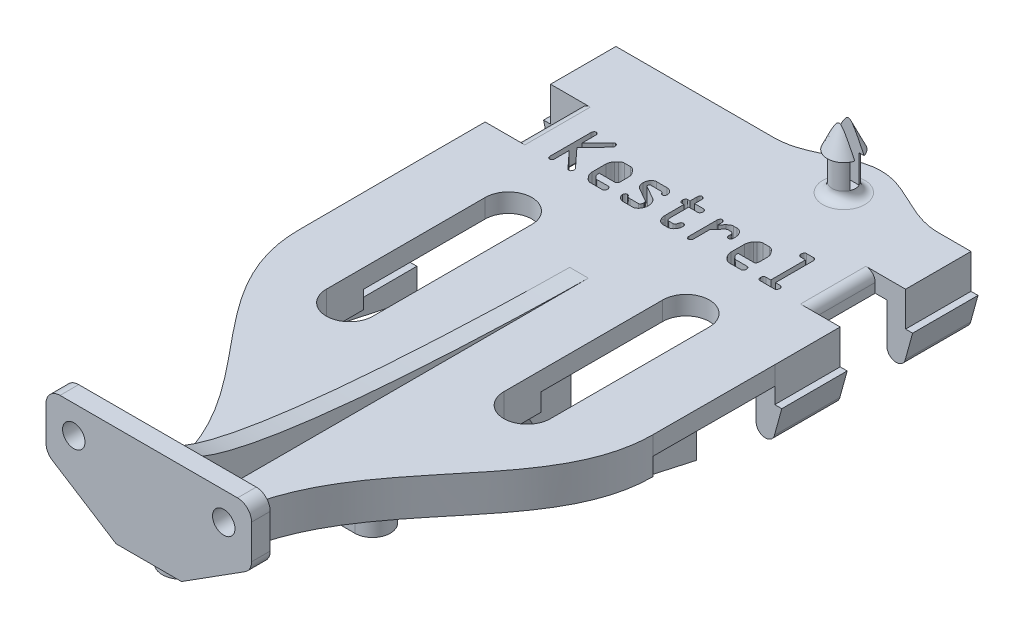
SolidWorks part; units mm, degrees
ref_plane "Front Plane" through (0, 0, 0) normal (0, 0, 1) x (1, 0, 0)
ref_plane "Top Plane" through (0, 0, 0) normal (0, 1, 0) x (1, 0, 0)
ref_plane "Right Plane" through (0, 0, 0) normal (1, 0, 0) x (0, 0, -1)
sketch "Sketch1" plane through (0, 0, 0) normal (0, 1, 0) x (1, 0, 0)
  line L0 (-19, 0) -> (-8.5, 0)
  line L1 (-19, 0) -> (-19, 5)
  line L2 (-19, 5) -> (19, 5)
  line L3 (19, 5) -> (19, 0)
  line L4 (0, 0) -> (0, -8) construction
  line L5 (0, -8) -> (0, -15) construction
  line L6 (-3.5, -15) -> (3.5, -15)
  line L7 (-3.5, -15) -> (-3.5, -5)
  line L8 (3.5, -15) -> (3.5, -5)
  line L9 (8.5, 0) -> (19, 0)
  arc A0 (3.5, -5) -> (8.5, 0) centre (8.5, -5) cw
  arc A1 (-3.5, -5) -> (-8.5, 0) centre (-8.5, -5) ccw
  point P4 (0, 0)
  point P14 (0, -15)
  point P17 (3.5, 0)
  dimension "D1" = 5
extrude "Boss-Extrude1" add sketch "Sketch1" along normal blind 2
sketch "Sketch2" plane through (0, 0, 0) normal (0, -1, 0) x (1, 0, 0)
  line L0 (-3.5, 15) -> (3.5, 15)
  line L1 (3.5, 15) -> (3.5, 13)
  line L2 (3.5, 15) -> (3.5, 5) construction
  line L3 (3.5, 13) -> (-3.5, 13)
  line L4 (-3.5, 5) -> (-3.5, 15) construction
  line L5 (-3.5, 13) -> (-3.5, 15)
extrude "Boss-Extrude2" add sketch "Sketch2" along normal blind 1.7
sketch "Sketch3" plane through (0, -1.7, 0) normal (0, -1, 0) x (1, 0, 0)
  line L0 (-3.5, 15) -> (-3.5, 6.3)
  line L1 (-3.5, 6.3) -> (3.5, 6.3)
  line L2 (3.5, 6.3) -> (3.5, 15)
  line L3 (3.5, 15) -> (-3.5, 15)
extrude "Boss-Extrude3" add sketch "Sketch3" along normal blind 2
sketch "Sketch5" plane through (0, 0, 0) normal (0, 0, 1) x (1, 0, 0)
  line L0 (0, -3.7) -> (0, 2) construction
  line L1 (3.5, -3.7) -> (-3.5, -3.7) construction
  line L2 (-3.5, 2) -> (3.5, 2) construction
  line L3 (-19, 0) -> (-19, -1.7)
  line L4 (-19, -1.7) -> (-19.75, -1.7)
  line L5 (-19, 0) -> (-17, 0)
  line L6 (-19, 0) -> (-8.5, 0) construction
  line L7 (-17, 0) -> (-17, -4.2915)
  line L9 (-19.75, -1.7) -> (-18.9642, -4.5567)
  line L10 (19.75, -1.7) -> (18.9642, -4.5567)
  line L11 (17, 0) -> (17, -4.2915)
  line L12 (19, 0) -> (17, 0)
  line L13 (19, -1.7) -> (19.75, -1.7)
  line L14 (19, 0) -> (19, -1.7)
  arc A0 (-17, -4.2915) -> (-18.9642, -4.5567) centre (-18, -4.2915) cw
  arc A1 (17, -4.2915) -> (18.9642, -4.5567) centre (18, -4.2915) ccw
  dimension "D1" = 1
extrude "Boss-Extrude5" add sketch "Sketch5" against normal up to surface (5 mm away) up to face at (0, 1, -5)
sketch "Sketch12" plane through (-3.5, 0, 0) normal (-1, 0, 0) x (0, 0, 1)
  line L0 (15, 2) -> (15, -3.7)
  line L1 (15, -0.85) -> (48, -0.85) construction
  line L2 (48, -1.85) -> (48, 0.15)
  line L5 (5, 2) -> (15, 2) construction
  line L6 (5, 2) -> (15, 2) construction
  line L7 (48, 0.15) -> (51.4434, 0.15) construction
  spline S0 degree 3 poles (48, 0.15) (45.4313, 0.15) (17.4134, 2) (15, 2) knots 0 0 0 0 1 1 1 1
  spline S1 degree 3 poles (48, -1.85) (45.4313, -1.85) (17.4134, -3.7) (15, -3.7) knots 0 0 0 0 1 1 1 1
  point P9 (48, -0.85)
extrude "Boss-Extrude10" add sketch "Sketch12" against normal up to surface (7 mm away) contours S0 L0 S1 L2 up to face at (3.5, -0.85, 9.825)
sketch "Sketch6" plane through (0, 0, 48) normal (0, 0, 1) x (1, 0, 0)
  line L0 (0, 8.9074) -> (0, 5.9074) construction
  line L1 (-8.025, 5.9074) -> (8.025, 5.9074) construction
  line L2 (-9.5, 8.9074) -> (9.5, 8.9074)
  line L3 (-11, 7.4074) -> (-11, 3.7322)
  line L4 (-10.3035, 2.4655) -> (-3.5, -1.85)
  line L5 (-3.5, -1.85) -> (3.5, -1.85)
  line L6 (11, 7.4074) -> (11, 3.7322)
  line L7 (10.3035, 2.4655) -> (3.5, -1.85)
  line L8 (3.5, -1.85) -> (-3.5, -1.85) construction
  line L9 (-3.5, -1.85) -> (3.5, -1.85)
  line L11 (3.5, -1.85) -> (-3.5, -1.85)
  line L12 (3.5, -1.85) -> (-3.5, -1.85)
  circle A0 centre (-8.025, 5.9074) radius 1.2
  circle A1 centre (8.025, 5.9074) radius 1.2
  arc A2 (11, 3.7322) -> (10.3035, 2.4655) centre (9.5, 3.7322) cw
  arc A3 (9.5, 8.9074) -> (11, 7.4074) centre (9.5, 7.4074) cw
  arc A4 (-9.5, 8.9074) -> (-11, 7.4074) centre (-9.5, 7.4074) ccw
  arc A5 (-11, 3.7322) -> (-10.3035, 2.4655) centre (-9.5, 3.7322) ccw
  point P5 (0, 5.9074)
  point P12 (0, 8.9074)
  dimension "D1" = 1.5
extrude "Boss-Extrude6" add sketch "Sketch6" against normal blind 2 contours L3 A5 L4 L7 A2 L6 A3 L2 A4 A0 A1 region at (0, 4.1004, 48)
sketch "Sketch8" plane through (0, 0, 0) normal (1, 0, 0) x (0, 0, -1)
  line L0 (-48, -1.85) -> (-17.2473, -11.6027)
sketch3d "3DSketch2"
  line L0 (3.5, -1.85, 48) -> (-3.5, -1.85, 48) construction
  line L1 (0, -1.85, 48) -> (0, -11.6027, 17.2473) construction
sketch "Sketch9" plane through (0, -29.0291, -37.7024) normal (0, 0.9532, -0.3023) x (1, 0, 0)
  line L0 (0, -51.7402) -> (0, -54.7402) construction
  line L1 (-8.025, -54.7402) -> (8.025, -54.7402) construction
  line L2 (-9.5, -51.7402) -> (9.5, -51.7402)
  line L3 (-11, -53.2402) -> (-11, -56.9154)
  line L4 (-10.3035, -58.182) -> (-3.5, -62.4976)
  line L5 (-3.5, -62.4976) -> (3.5, -62.4976)
  line L6 (11, -53.2402) -> (11, -56.9154)
  line L7 (10.3035, -58.182) -> (3.5, -62.4976)
  line L8 (3.5, -89.9089) -> (-3.5, -89.9089) construction
  line L9 (-3.5, -57.2253) -> (3.5, -57.2253) construction
  line L10 (0, -57.2253) -> (0, -62.4976) construction
  line L11 (3.5, -62.4976) -> (-3.5, -62.4976) construction
  line L12 (3.5, -89.9089) -> (-3.5, -89.9089)
  line L13 (-3.5, -62.4976) -> (3.5, -62.4976)
  circle A0 centre (-8.025, -54.7402) radius 1.2
  circle A1 centre (8.025, -54.7402) radius 1.2
  arc A2 (11, -56.9154) -> (10.3035, -58.182) centre (9.5, -56.9154) cw
  arc A3 (9.5, -51.7402) -> (11, -53.2402) centre (9.5, -53.2402) cw
  arc A4 (-9.5, -51.7402) -> (-11, -53.2402) centre (-9.5, -53.2402) ccw
  arc A5 (-11, -56.9154) -> (-10.3035, -58.182) centre (-9.5, -56.9154) ccw
  point P5 (0, -54.7402)
  point P12 (0, -51.7402)
  point P30 (0, -62.4976)
  dimension "D1" = 1.5
extrude "Boss-Extrude8" [suppressed] add sketch "Sketch9" along normal blind 2 contours A5 L3 A4 L2 A3 L6 A2 L7 L5 L4 A0 A1
sketch "Sketch11" plane through (0, 0, -5) normal (0, 0, -1) x (-1, 0, 0)
  line L10 (-19, 2) -> (-19, -1.7)
  line L11 (-19, -1.7) -> (-19.75, -1.7)
  line L12 (-19.75, -1.7) -> (-18.9642, -4.5567)
  line L13 (-17, -4.2915) -> (-17, 0)
  line L14 (-17, 0) -> (17, 0)
  line L15 (17, 0) -> (17, -4.2915)
  line L16 (18.9642, -4.5567) -> (19.75, -1.7)
  line L17 (19.75, -1.7) -> (19, -1.7)
  line L18 (19, -1.7) -> (19, 2)
  line L19 (19, 2) -> (-19, 2)
  line L20 (-19, 2) -> (-19, -1.7)
  line L21 (-19, -1.7) -> (-19.75, -1.7)
  line L22 (-19.75, -1.7) -> (-18.9642, -4.5567)
  line L23 (-17, -4.2915) -> (-17, 0)
  line L24 (-17, 0) -> (17, 0)
  line L25 (17, 0) -> (17, -4.2915)
  line L26 (18.9642, -4.5567) -> (19.75, -1.7)
  line L27 (19.75, -1.7) -> (19, -1.7)
  line L28 (19, -1.7) -> (19, 2)
  line L29 (19, 2) -> (-19, 2)
  arc A2 (-18.9642, -4.5567) -> (-17, -4.2915) centre (-18, -4.2915) ccw
  arc A3 (17, -4.2915) -> (18.9642, -4.5567) centre (18, -4.2915) ccw
  arc A4 (-18.9642, -4.5567) -> (-17, -4.2915) centre (-18, -4.2915) ccw
  arc A5 (17, -4.2915) -> (18.9642, -4.5567) centre (18, -4.2915) ccw
  dimension "D1" = 0
extrude "Boss-Extrude9" add sketch "Sketch11" along normal blind 5
sketch "Sketch13" plane through (0, 0, -10) normal (0, 0, -1) x (-1, 0, 0)
  line L0 (-17, 0) -> (-17, 2)
  line L1 (17, 0) -> (17, 2)
  line L2 (-17, 2) -> (-19, 2)
  line L10 (19, 2) -> (-19, 2)
  line L11 (-19, 2) -> (-19, -1.7)
  line L12 (-19, -1.7) -> (-19.75, -1.7)
  line L13 (-19.75, -1.7) -> (-18.9642, -4.5567)
  line L14 (-17, -4.2915) -> (-17, 0)
  line L15 (-17, 0) -> (17, 0)
  line L16 (17, 0) -> (17, -4.2915)
  line L17 (18.9642, -4.5567) -> (19.75, -1.7)
  line L18 (19.75, -1.7) -> (19, -1.7)
  line L19 (19, -1.7) -> (19, 2)
  line L20 (19, 2) -> (17, 2)
  line L21 (-19, 2) -> (-19, -1.7)
  line L22 (-19, -1.7) -> (-19.75, -1.7)
  line L23 (-19.75, -1.7) -> (-18.9642, -4.5567)
  line L24 (-17, -4.2915) -> (-17, 0)
  line L26 (17, 0) -> (17, -4.2915)
  line L27 (18.9642, -4.5567) -> (19.75, -1.7)
  line L28 (19.75, -1.7) -> (19, -1.7)
  line L29 (19, -1.7) -> (19, 2)
  arc A2 (-18.9642, -4.5567) -> (-17, -4.2915) centre (-18, -4.2915) ccw
  arc A3 (17, -4.2915) -> (18.9642, -4.5567) centre (18, -4.2915) ccw
  arc A4 (-18.9642, -4.5567) -> (-17, -4.2915) centre (-18, -4.2915) ccw
  arc A5 (17, -4.2915) -> (18.9642, -4.5567) centre (18, -4.2915) ccw
  dimension "D1" = 0
extrude "Boss-Extrude11" add sketch "Sketch13" along normal blind 11
sketch "Sketch14" [suppressed] plane through (0, 0, 0) normal (1, 0, 0) x (0, 0, -1)
  line L0 (-21.4898, -4.5318) -> (-16.4946, -9.5269) construction
  line L2 (-19.0398, -6.9817) -> (-21.6386, -4.383) construction
  line L4 (-25, 3.9255) -> (-25, 7.5698) construction
  line L6 (-25, 9.4074) -> (-25, 5.7322) construction
  line L8 (-21.4898, -4.5318) -> (-23.7806, -2.241)
  line L9 (-23.7806, -2.241) -> (-20.5918, -2.8431)
  line L10 (-25, 3.9255) -> (-25, 0.342)
  line L51 (-25, 0.342) -> (-21.429, 0.9803)
  arc A0 (-21.429, 0.9803) -> (-25, 3.9255) centre (-22, 3.9255) cw
  arc A1 (-21.4898, -4.5318) -> (-20.5918, -2.8431) centre (-20.7827, -3.8247) cw
  spline S0 degree 3 poles (2744.4383, -1158.1805) (-2916.1759, 1174.945) (2874.0779, -1177.5151) (-2786.653, 1143.8803) knots -6.32124 -6.32124 -6.32124 -6.32124 7.304164 7.304164 7.304164 7.304164 only from (-23.7806, -2.241) to (-15, -3.7) construction
  spline S1 degree 3 poles (-2786.706, -1145.6021) (2873.7453, 1175.6786) (-2915.4391, -1176.3458) (2743.3321, 1156.0245) knots -6.104431 -6.104431 -6.104431 -6.104431 7.520128 7.520128 7.520128 7.520128 only from (-15, 2) to (-25, 0.342) construction
  spline S2 degree 3 poles (-20.5918, -2.8431) (-18.3357, -3.2818) (-16.1475, -3.7) (-15, -3.7) knots 0.524559 0.524559 0.524559 0.524559 1 1 1 1 construction
  spline S3 degree 3 poles (-15, 2) (-16.2892, 2) (-18.8922, 1.4721) (-21.429, 0.9803) knots 0.199776 0.199776 0.199776 0.199776 0.733944 0.733944 0.733944 0.733944 construction
  dimension "D1" = 3
  dimension "D2" = 1
extrude "Boss-Extrude12" [suppressed] add sketch "Sketch14" along normal blind 1 and the other way blind 1 contours L51 A0 L10 | L8 A1 L9
fillet "Fillet1" [suppressed] radius 3
sketch "Sketch18" plane through (0, 0, 0) normal (1, 0, 0) x (0, 0, -1)
  line L0 (-46, 8.5867) -> (-46, 16.5411)
  line L1 (0, 2) -> (9.2636, 2.3571)
  line L2 (-46, 8.5867) -> (-46, 0.2267)
  line L3 (-46, 0.2267) -> (0, 2)
  spline S0 degree 3 poles (-46, 8.5867) (-46, 2.3837) (-1.9861, 1.9234) (0, 2) knots 0 0 0 0 1 1 1 1
  point P5 (-46, 0.2267)
extrude "Boss-Extrude16" add sketch "Sketch18" along normal blind 1 and the other way blind 1 contours L2 L3 region at (0, 2.6128, 33.5816)
sketch "Sketch19" plane through (0, 0, -10) normal (0, 0, -1) x (-1, 0, 0)
  line L4 (-17, 0) -> (17, 0)
  line L5 (17, 0) -> (17, 2)
  line L6 (17, 2) -> (-17, 2)
  line L7 (-17, 2) -> (-17, 0)
  line L8 (-17, 0) -> (17, 0)
  line L9 (17, 0) -> (17, 2)
  line L10 (17, 2) -> (-17, 2)
  line L11 (-17, 2) -> (-17, 0)
  dimension "D1" = 0
extrude "Boss-Extrude17" add sketch "Sketch19" along normal up to surface (11 mm away) up to face at (18.433, -1.5178, -21)
sketch "Sketch20" plane through (0, 2, 0) normal (0, 1, 0) x (1, 0, 0)
  line L0 (-19.75, 0) -> (-19.75, 21) construction
  line L1 (19.75, 0) -> (19.75, 21) construction
  line L4 (-23.75, 14) -> (-15.75, 14)
  line L5 (-23.75, 14) -> (-23.75, 7)
  line L6 (-23.75, 7) -> (-15.75, 7)
  line L7 (-15.75, 14) -> (-15.75, 7)
  line L8 (-23.75, 14) -> (-15.75, 7) construction
  line L9 (-23.75, 7) -> (-15.75, 14) construction
  line L10 (15.75, 14) -> (23.75, 14)
  line L11 (15.75, 14) -> (15.75, 7)
  line L12 (15.75, 7) -> (23.75, 7)
  line L13 (23.75, 14) -> (23.75, 7)
  line L14 (15.75, 14) -> (23.75, 7) construction
  line L15 (15.75, 7) -> (23.75, 14) construction
  point P6 (-19.75, 10.5)
  point P15 (19.75, 10.5)
extrude "Cut-Extrude2" cut sketch "Sketch20" against normal blind 10.2
fillet "Fillet3" radius 1 2 edges at (15.75, 2, -10.5) (-15.75, 2, -10.5)
sketch "Sketch22" plane through (0, 2, 0) normal (0, 1, 0) x (1, 0, 0)
  line L0 (-15.75, 7) -> (15.75, 7) construction
  text T0 "Kestrel" font "OCR A Extended" height 5
extrude "Cut-Extrude4" cut sketch "Sketch22" against normal up to surface (2 mm away) up to face at (0, 0, -5.1151)
delete or keep bodies "Body-Delete/Keep 1" type delete bodies bodies 125 126
sketch "Sketch23" plane through (0, 2, 0) normal (0, 1, 0) x (1, 0, 0)
  circle A0 centre (6.7297, 19.6566) radius 1.375 construction
  circle A1 centre (6.7297, 19.6566) radius 1.375 construction
  circle A2 centre (6.7297, 19.6566) radius 1.25
sketch "Sketch25" plane through (0, 2, 0) normal (0, 1, 0) x (1, 0, 0)
  line L0 (-19, 21) -> (19, 21) construction
  line L1 (15.4974, 21) -> (27.7055, 21) construction
  line L2 (10.4974, 21) -> (15.4974, 21)
  line L3 (2.9621, 21) -> (-2.0379, 21)
  line L4 (-2.0379, 21) -> (-6.3002, 21) construction
  line L5 (2.9621, 21) -> (10.4974, 21)
  circle A0 centre (6.7297, 19.6566) radius 4 construction
  spline S0 degree 3 poles (6.7297, 23.6566) (9.7835, 23.6566) (12.1916, 21) (15.4974, 21) knots 0 0 0 0 1 1 1 1
  spline S1 degree 3 poles (-2.0379, 21) (1.2679, 21) (3.676, 23.6566) (6.7297, 23.6566) knots 0 0 0 0 1 1 1 1
extrude "Boss-Extrude18" add sketch "Sketch25" against normal up to surface (2 mm away) contours L3 S1 S0 L2 L5 up to face at (-7.4332, 0, -8.6263)
extrude "Boss-Extrude19" add sketch "Sketch23" along normal blind 4
fillet "Fillet5" radius 1 1 edges at (6.7297, 2, -18.4066)
sketch "Sketch27" plane through (0, 2, 0) normal (0, 1, 0) x (1, 0, 0)
  line L0 (-19, 0) -> (19, 0)
  line L1 (-3.5, -15) -> (3.5, -15)
  line L3 (0, 0) -> (0, 4.6764) construction
  line L4 (-3.5, -15) -> (-3.5, -46) construction
  spline S0 degree 2 poles (-19, 0) (-3.5, -6.737) (-3.5, -15) knots 0 0 0 1 1 1
  spline S1 degree 2 poles (19, 0) (3.5, -6.737) (3.5, -15) knots 0 0 0 1 1 1
extrude "Boss-Extrude20" add sketch "Sketch27" against normal up to surface (2 mm away) up to face at (-7.4332, 0, -8.6263)
sketch "Sketch28" plane through (0, 0, 0) normal (0, -1, 0) x (1, 0, 0)
  line L0 (-3.5, 13) -> (-18.9642, 13)
  line L1 (3.5, 13) -> (18.9642, 13)
  line L2 (-18.9642, 0) -> (-18.9642, 13) construction
  line L3 (18.9642, 13) -> (18.9642, 0) construction
  line L4 (-3.5, 47.0417) -> (-3.5, 45.0417) construction
  line L5 (-3.5, 48) -> (-3.5, 15) construction
  line L6 (3.5, 47.0417) -> (3.5, 45.0417)
  line L7 (3.5, 15) -> (3.5, 48) construction
  line L8 (0, 15) -> (0, 21.0954) construction
  line L9 (3.5, 15) -> (-3.5, 15) construction
  line L10 (-3.5, 13) -> (3.5, 13)
  line L12 (-3.5, 45.0417) -> (3.5, 45.0417)
  spline S0 degree 3 poles (-18.9642, 13) (-18.9642, 24.9756) (-3.5, 30.7082) (-3.5, 45.0417) knots 0 0 0 0 1 1 1 1
  spline S1 degree 3 poles (18.9642, 13) (18.9642, 24.9756) (3.5, 30.7082) (3.5, 45.0417) knots 0 0 0 0 1 1 1 1
  point P9 (0, 0)
extrude "Boss-Extrude21" add sketch "Sketch28" along normal blind 1.9 contours L12 S0 L0 L10 L1 S1
sketch "Sketch29" plane through (-3.5, 0, 0) normal (-1, 0, 0) x (0, 0, 1)
  line L0 (6.3, -3.7) -> (6.3, -10.4)
  line L1 (13, -3.7) -> (6.3, -3.7)
  line L2 (6.3, -10.4) -> (3.1823, -10.4) construction
  spline S0 degree 3 poles (6.3, -10.4) (9.9895, -10.4) (9.9638, -3.7) (13, -3.7) knots 0 0 0 0 1 1 1 1
  line M3 (6.3, -3.7) -> (15, -3.7)
extrude "Boss-Extrude22" add sketch "Sketch29" against normal up to surface (7 mm away) contours L0 M3 region at (-3.5, -6.3581, 8.3061) up to face at (3.5, -1.3426, 23.4736)
sketch "Sketch30" plane through (0, -3.7, 0) normal (0, -1, 0) x (1, 0, 0)
  line L8 (6.45, 32.4) -> (2.8797, 32.4)
  line L9 (2.65, 32.7091) -> (1.997, 44.6591)
  line L10 (-1.997, 44.6591) -> (-2.65, 32.7091)
  line L11 (-2.8797, 32.4) -> (-6.45, 32.4)
  line L12 (-6.45, 28.6) -> (-3.2953, 28.6)
  line L13 (-3.2953, 28.6) -> (-1.9922, 13.8737)
  line L14 (1.9922, 13.8737) -> (3.2953, 28.6)
  line L15 (3.2953, 28.6) -> (6.45, 28.6)
  line L16 (0, 46.55) -> (0, 12.05) construction
  line L17 (0, 13) -> (0, 48) construction
  line L18 (3.5, 13) -> (-3.5, 13) construction
  line L19 (3.5, 48) -> (-3.5, 48) construction
  line L20 (-2.0139, 30.5) -> (2.0139, 30.5) construction
  arc A6 (2.8797, 32.4) -> (2.65, 32.7091) centre (0, 30.5) ccw
  arc A7 (1.997, 44.6591) -> (-1.997, 44.6591) centre (0, 44.55) ccw
  arc A8 (-2.65, 32.7091) -> (-2.8797, 32.4) centre (0, 30.5) ccw
  arc A9 (-6.45, 32.4) -> (-6.45, 28.6) centre (-6.45, 30.5) ccw
  arc A10 (-1.9922, 13.8737) -> (1.9922, 13.8737) centre (0, 14.05) ccw
  arc A11 (6.45, 28.6) -> (6.45, 32.4) centre (6.45, 30.5) ccw
  circle A12 centre (6.45, 30.5) radius 0.6
  circle A13 centre (4.45, 30.5) radius 0.6
  circle A14 centre (0, 13.65) radius 0.6
  circle A15 centre (0, 15.65) radius 0.6
  circle A16 centre (0, 17.65) radius 0.6
  circle A17 centre (0, 19.65) radius 0.6
  circle A18 centre (0, 21.65) radius 0.6
  circle A19 centre (0, 23.65) radius 0.6
  circle A20 centre (0, 25.65) radius 0.6
  circle A21 centre (-6.45, 30.5) radius 0.6
  circle A22 centre (-4.45, 30.5) radius 0.6
  circle A23 centre (0, 34.95) radius 0.6
  circle A24 centre (0, 36.95) radius 0.6
  circle A25 centre (0, 38.95) radius 0.6
  circle A26 centre (0, 40.95) radius 0.6
  circle A27 centre (0, 42.95) radius 0.6
  circle A28 centre (0, 44.95) radius 0.6
  point P63 (0, 30.5)
  line M30 (-3.5, 13) -> (3.5, 13)
  line M32 (3.5, 15) -> (-3.5, 15)
extrude "Boss-Extrude23" add sketch "Sketch30" against normal up to surface (3.7 mm away) contours L15 A11 L8 A6 L9 A7 L10 A8 L11 A9 L12 L13 L14 A28 A27 A26 A25 A24 A23 A22 A21 A20 A19 A18 A17 A16 A15 A13 A12 M32 | A10 L14 L13 A14 M30 M32 | A10 M30 region at (0, -3.7, 30.121) region at (1.9959, -3.7, 14.4409) region at (0, -3.7, 12.611) up to face at (-9.3281, 0, 17.7552)
extrude "Cut-Extrude5" cut sketch "Sketch30<3>" against normal blind 4 contours A14 | A15 | A16 | A17 | A18 | A19 | A20 | A12 | A13 | A22 | A21 | A23 | A24 | A25 | A26 | A27 | A28 region at (6.45, -3.7, 30.5) region at (4.45, -3.7, 30.5) region at (0, -3.7, 13.65) region at (0, -3.7, 15.65) region at (0, -3.7, 17.65) region at (0, -3.7, 19.65) region at (0, -3.7, 21.65) region at (0, -3.7, 23.65) region at (0, -3.7, 25.65) region at (-6.45, -3.7, 30.5) region at (-4.45, -3.7, 30.5) region at (0, -3.7, 34.95) region at (0, -3.7, 36.95) region at (0, -3.7, 38.95) region at (0, -3.7, 40.95) region at (0, -3.7, 42.95) region at (0, -3.7, 44.95)
sketch "Sketch30<3>" plane through (0, -3.7, 0) normal (0, -1, 0) x (1, 0, 0) same geometry as "Sketch30"
sketch "Sketch32" plane through (-3.5, 0, 0) normal (-1, 0, 0) x (0, 0, 1)
  line L0 (13, -1.7) -> (13, 0)
  line L1 (13, 0) -> (11.1713, 0)
  line L2 (0, 0) -> (13, 0) construction
  line L3 (11.1713, 0) -> (11.1713, -1.7)
  line L4 (13, -1.7) -> (6.3, -1.7) construction
  line L5 (11.1713, -1.7) -> (13, -1.7)
  line M8 (13, -1.7) -> (6.3, -1.7)
extrude "Cut-Extrude6" cut sketch "Sketch32" against normal up to surface (7 mm away) contours L1 L3 L0 M8 region at (-3.5, -0.85, 12.0856) up to face at (3.5, -3.1217, 15.0438)
extrude "Cut-Extrude7" cut sketch "Sketch30<4>" along normal blind 3
sketch "Sketch30<4>" plane through (0, -3.7, 0) normal (0, -1, 0) x (1, 0, 0) same geometry as "Sketch30"
sketch "Sketch33" plane through (0, 2, 0) normal (0, 1, 0) x (1, 0, 0)
  line L0 (-19, 0) -> (-18.9642, -13)
  line L1 (19, 0) -> (18.9642, -13)
  line L2 (-3.5, -45.0417) -> (-3.5, -46)
  line L3 (-3.5, -46) -> (3.5, -46)
  line L4 (3.5, -46) -> (3.5, -45.0417)
  line L5 (-19, 0) -> (19, 0)
  spline S0 degree 3 poles (1750.4725, 917.6448) (-1878.3213, -854.5874) (1839.3304, 827.4912) (-1726.4682, -1057.6547) knots -3.412588 -3.412588 -3.412588 -3.412588 4.379038 4.379038 4.379038 4.379038 only from (-18.9642, -13) to (-3.5, -45.0417) construction
  spline S1 degree 3 poles (-1750.4725, 917.6448) (1878.3213, -854.5874) (-1839.3304, 827.4912) (1726.4682, -1057.6547) knots -3.412588 -3.412588 -3.412588 -3.412588 4.379038 4.379038 4.379038 4.379038 only from (18.9642, -13) to (3.5, -45.0417) construction
  spline S2 degree 3 poles (-18.9642, -13) (-18.9642, -24.9756) (-3.5, -30.7082) (-3.5, -45.0417) knots 0 0 0 0 1 1 1 1
  spline S3 degree 3 poles (18.9642, -13) (18.9642, -24.9756) (3.5, -30.7082) (3.5, -45.0417) knots 0 0 0 0 1 1 1 1
extrude "Boss-Extrude24" add sketch "Sketch33" against normal blind 2
sketch "Sketch34" plane through (0, 2, 0) normal (0, 1, 0) x (1, 0, 0)
  line L0 (-19, 0) -> (0, 0) construction
  line L1 (-9.5, 0) -> (-9.5, -17) construction
  line L2 (0, 0) -> (0, -12.9125) construction
  line L3 (-7, -17) -> (-7, 0)
  line L4 (-12, 0) -> (-12, -17)
  line L5 (7, -17) -> (7, 0)
  line L6 (12, 0) -> (12, -17)
  arc A0 (-7, 0) -> (-12, 0) centre (-9.5, 0) ccw
  arc A1 (-12, -17) -> (-7, -17) centre (-9.5, -17) ccw
  arc A2 (12, -17) -> (7, -17) centre (9.5, -17) cw
  arc A3 (7, 0) -> (12, 0) centre (9.5, 0) cw
extrude "Cut-Extrude8" cut sketch "Sketch34" against normal blind 12
sketch "Sketch35" plane through (18.9999, 0, 0.0523) normal (1, 0, 0.0028) x (0.0028, 0, -1)
  line L0 (-6.2903, -1.7) -> (-12.9477, -1.7)
  line L1 (-12.9477, -1.9) -> (-12.9477, 0) construction
  line L2 (-6.2903, -1.7) -> (-12.9903, -1.7) construction
  line L3 (-12.9477, -1.7) -> (-19.9477, -1.7)
  line L4 (-6.2903, -1.7) -> (-6.2903, -4.7)
  line L5 (-19.9477, -1.7) -> (-6.2903, -4.7)
extrude "Boss-Extrude25" add sketch "Sketch35" against normal blind 4 from offset 2 offset against normal yes
mirror "Mirror1" about plane through (0, 0, 0) normal (1, 0, 0) of "Boss-Extrude25"
fillet "Fillet6" radius 10 2 edges at (14.9474, -1.9, 19.0785) (-14.9474, -1.9, 19.0785)
sketch "Sketch36" plane through (0, 6, 0) normal (0, 1, 0) x (1, 0, 0)
  circle A0 centre (6.7297, 19.6566) radius 1.75
extrude "Boss-Extrude26" add sketch "Sketch36" along normal blind 10 draft 25
sketch "Sketch37" plane through (0, 2, 0) normal (0, 1, 0) x (1, 0, 0)
  line L1 (4.2297, 20.1566) -> (9.2297, 20.1566)
  line L2 (4.2297, 20.1566) -> (4.2297, 19.1566)
  line L3 (4.2297, 19.1566) -> (9.2297, 19.1566)
  line L4 (9.2297, 20.1566) -> (9.2297, 19.1566)
  line L5 (4.2297, 20.1566) -> (9.2297, 19.1566) construction
  line L6 (4.2297, 19.1566) -> (9.2297, 20.1566) construction
  point P0 (6.7297, 19.6566)
extrude "Cut-Extrude9" cut sketch "Sketch37" along normal blind 10 from offset 1
